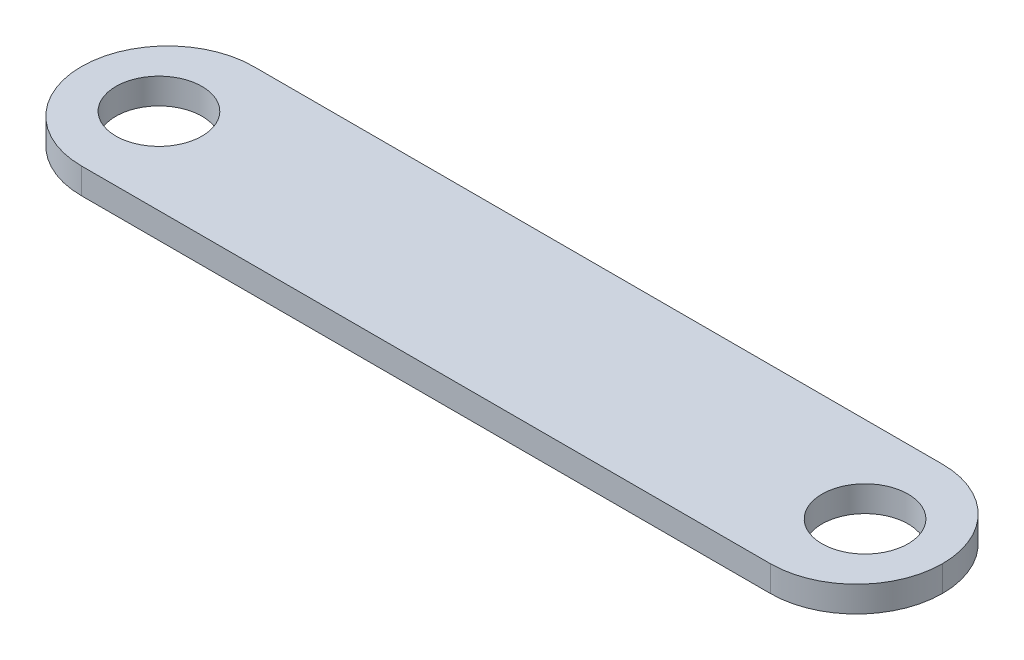
SolidWorks part; units mm, degrees
ref_plane "Front Plane" through (0, 0, 0) normal (0, 0, 1) x (1, 0, 0)
ref_plane "Top Plane" through (0, 0, 0) normal (0, 1, 0) x (1, 0, 0)
ref_plane "Right Plane" through (0, 0, 0) normal (1, 0, 0) x (0, 0, -1)
sketch "Sketch2" plane through (0, 0, 0) normal (0, 1, 0) x (1, 0, 0)
  line L1 (0, 0) -> (100, 0)
  line L2 (0, 0) -> (0, 20)
  line L3 (0, 20) -> (100, 20)
  line L4 (100, 0) -> (100, 20)
  dimension "D1" = 100
  dimension "D2" = 20
extrude "Boss-Extrude1" add sketch "Sketch2" along normal blind 3
sketch "Sketch3" plane through (0, 3, 0) normal (0, 1, 0) x (1, 0, 0)
  line L0 (100, 20) -> (0, 20) construction
  line L1 (0, 20) -> (0, 0) construction
  circle A0 centre (9, 10) radius 5
  dimension "D1" = 10
  dimension "D2" = 9
extrude "Cut-Extrude1" cut sketch "Sketch3" against normal through all
sketch "Sketch4" plane through (0, 3, 0) normal (0, 1, 0) x (1, 0, 0)
  line L0 (100, 20) -> (0, 20) construction
  line L1 (100, 0) -> (100, 20) construction
  circle A0 centre (91, 10) radius 5
  dimension "D1" = 10
  dimension "D2" = 9
extrude "Cut-Extrude2" cut sketch "Sketch4" against normal through all
fillet "Fillet1" radius 10 2 edges at (0, 1.5, -20) (0, 1.5, 0)
fillet "Fillet2" radius 10 2 edges at (100, 1.5, -20) (100, 1.5, 0)
